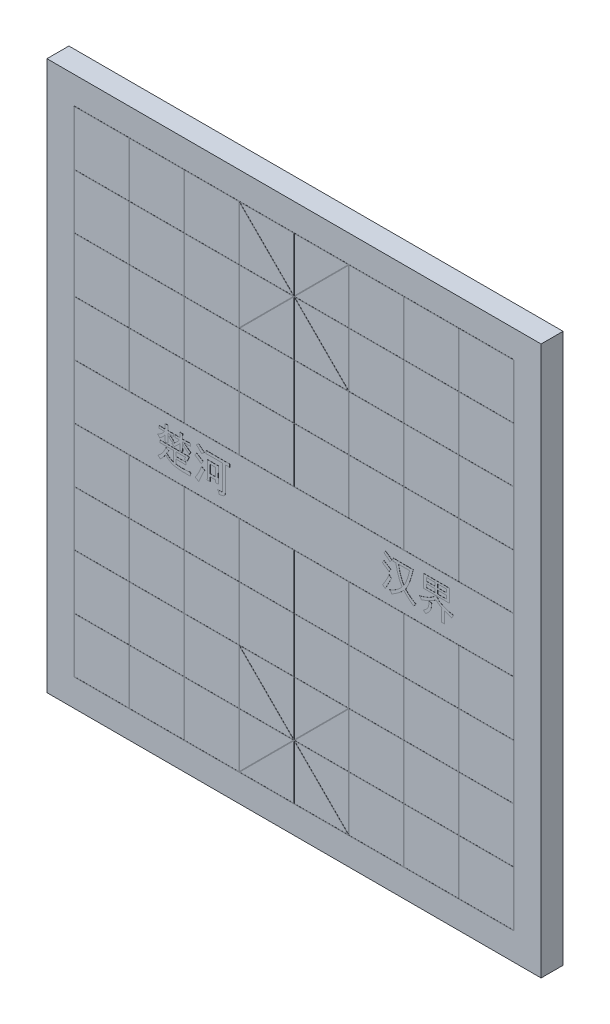
SolidWorks part; units mm, degrees
ref_plane "前视基准面" through (0, 0, 0) normal (0, 0, 1) x (1, 0, 0)
ref_plane "上视基准面" through (0, 0, 0) normal (0, 1, 0) x (1, 0, 0)
ref_plane "右视基准面" through (0, 0, 0) normal (1, 0, 0) x (0, 0, -1)
other "Configuration Table"
sketch "草图1" plane through (0, 0, 0) normal (0, 0, 1) x (1, 0, 0)
  line L1 (-157.5, -175) -> (157.5, -175)
  line L2 (-157.5, -175) -> (-157.5, 175)
  line L3 (-157.5, 175) -> (157.5, 175)
  line L4 (157.5, -175) -> (157.5, 175)
  dimension "D1" = 157.5
  dimension "D2" = 157.5
  dimension "D3" = 175
  dimension "D4" = 175
extrude "Board315x350x14" add sketch "草图1" against normal blind 14
sketch "草图2" plane through (0, 0, 0) normal (0, 0, 1) x (1, 0, 0)
  line L1 (-140, -157.66) -> (140, -157.66)
  line L2 (-140, -157.66) -> (-140, -157.34)
  line L3 (-140, -157.34) -> (140, -157.34)
  line L4 (140, -157.66) -> (140, -157.34)
  line L6 (-140, -122.66) -> (140, -122.66)
  line L7 (-140, -122.66) -> (-140, -122.34)
  line L8 (-140, -122.34) -> (140, -122.34)
  line L9 (140, -122.66) -> (140, -122.34)
  line L11 (-140, -87.66) -> (140, -87.66)
  line L12 (-140, -87.66) -> (-140, -87.34)
  line L13 (-140, -87.34) -> (140, -87.34)
  line L14 (140, -87.66) -> (140, -87.34)
  line L16 (-140, -52.66) -> (140, -52.66)
  line L17 (-140, -52.66) -> (-140, -52.34)
  line L18 (-140, -52.34) -> (140, -52.34)
  line L19 (140, -52.66) -> (140, -52.34)
  line L21 (-140, -17.66) -> (140, -17.66)
  line L22 (-140, -17.66) -> (-140, -17.34)
  line L23 (-140, -17.34) -> (140, -17.34)
  line L24 (140, -17.66) -> (140, -17.34)
  line L26 (-140, 17.34) -> (140, 17.34)
  line L27 (-140, 17.34) -> (-140, 17.66)
  line L28 (-140, 17.66) -> (140, 17.66)
  line L29 (140, 17.34) -> (140, 17.66)
  line L31 (-140, 52.34) -> (140, 52.34)
  line L32 (-140, 52.34) -> (-140, 52.66)
  line L33 (-140, 52.66) -> (140, 52.66)
  line L34 (140, 52.34) -> (140, 52.66)
  line L36 (-140, 87.34) -> (140, 87.34)
  line L37 (-140, 87.34) -> (-140, 87.66)
  line L38 (-140, 87.66) -> (140, 87.66)
  line L39 (140, 87.34) -> (140, 87.66)
  line L41 (-140, 122.34) -> (140, 122.34)
  line L42 (-140, 122.34) -> (-140, 122.66)
  line L43 (-140, 122.66) -> (140, 122.66)
  line L44 (140, 122.34) -> (140, 122.66)
  line L46 (-140, 157.34) -> (140, 157.34)
  line L47 (-140, 157.34) -> (-140, 157.66)
  line L48 (-140, 157.66) -> (140, 157.66)
  line L49 (140, 157.34) -> (140, 157.66)
extrude "Ten_ranks" add sketch "草图2" along normal blind 0.05
sketch "草图3" plane through (0, 0, 0) normal (0, 0, 1) x (1, 0, 0)
  line L1 (-140.16, -157.5) -> (-139.84, -157.5)
  line L2 (-140.16, -157.5) -> (-140.16, 157.5)
  line L3 (-140.16, 157.5) -> (-139.84, 157.5)
  line L4 (-139.84, -157.5) -> (-139.84, 157.5)
  line L6 (-105.16, -157.5) -> (-104.84, -157.5)
  line L7 (-105.16, -157.5) -> (-105.16, -17.5)
  line L8 (-105.16, -17.5) -> (-104.84, -17.5)
  line L9 (-104.84, -157.5) -> (-104.84, -17.5)
  line L11 (-105.16, 17.5) -> (-104.84, 17.5)
  line L12 (-105.16, 17.5) -> (-105.16, 157.5)
  line L13 (-105.16, 157.5) -> (-104.84, 157.5)
  line L14 (-104.84, 17.5) -> (-104.84, 157.5)
  line L16 (-70.16, -157.5) -> (-69.84, -157.5)
  line L17 (-70.16, -157.5) -> (-70.16, -17.5)
  line L18 (-70.16, -17.5) -> (-69.84, -17.5)
  line L19 (-69.84, -157.5) -> (-69.84, -17.5)
  line L21 (-70.16, 17.5) -> (-69.84, 17.5)
  line L22 (-70.16, 17.5) -> (-70.16, 157.5)
  line L23 (-70.16, 157.5) -> (-69.84, 157.5)
  line L24 (-69.84, 17.5) -> (-69.84, 157.5)
  line L26 (-35.16, -157.5) -> (-34.84, -157.5)
  line L27 (-35.16, -157.5) -> (-35.16, -17.5)
  line L28 (-35.16, -17.5) -> (-34.84, -17.5)
  line L29 (-34.84, -157.5) -> (-34.84, -17.5)
  line L31 (-35.16, 17.5) -> (-34.84, 17.5)
  line L32 (-35.16, 17.5) -> (-35.16, 157.5)
  line L33 (-35.16, 157.5) -> (-34.84, 157.5)
  line L34 (-34.84, 17.5) -> (-34.84, 157.5)
  line L36 (-0.16, -157.5) -> (0.16, -157.5)
  line L37 (-0.16, -157.5) -> (-0.16, -17.5)
  line L38 (-0.16, -17.5) -> (0.16, -17.5)
  line L39 (0.16, -157.5) -> (0.16, -17.5)
  line L41 (-0.16, 17.5) -> (0.16, 17.5)
  line L42 (-0.16, 17.5) -> (-0.16, 157.5)
  line L43 (-0.16, 157.5) -> (0.16, 157.5)
  line L44 (0.16, 17.5) -> (0.16, 157.5)
  line L46 (34.84, -157.5) -> (35.16, -157.5)
  line L47 (34.84, -157.5) -> (34.84, -17.5)
  line L48 (34.84, -17.5) -> (35.16, -17.5)
  line L49 (35.16, -157.5) -> (35.16, -17.5)
  line L51 (34.84, 17.5) -> (35.16, 17.5)
  line L52 (34.84, 17.5) -> (34.84, 157.5)
  line L53 (34.84, 157.5) -> (35.16, 157.5)
  line L54 (35.16, 17.5) -> (35.16, 157.5)
  line L56 (69.84, -157.5) -> (70.16, -157.5)
  line L57 (69.84, -157.5) -> (69.84, -17.5)
  line L58 (69.84, -17.5) -> (70.16, -17.5)
  line L59 (70.16, -157.5) -> (70.16, -17.5)
  line L61 (69.84, 17.5) -> (70.16, 17.5)
  line L62 (69.84, 17.5) -> (69.84, 157.5)
  line L63 (69.84, 157.5) -> (70.16, 157.5)
  line L64 (70.16, 17.5) -> (70.16, 157.5)
  line L66 (104.84, -157.5) -> (105.16, -157.5)
  line L67 (104.84, -157.5) -> (104.84, -17.5)
  line L68 (104.84, -17.5) -> (105.16, -17.5)
  line L69 (105.16, -157.5) -> (105.16, -17.5)
  line L71 (104.84, 17.5) -> (105.16, 17.5)
  line L72 (104.84, 17.5) -> (104.84, 157.5)
  line L73 (104.84, 157.5) -> (105.16, 157.5)
  line L74 (105.16, 17.5) -> (105.16, 157.5)
  line L76 (139.84, -157.5) -> (140.16, -157.5)
  line L77 (139.84, -157.5) -> (139.84, 157.5)
  line L78 (139.84, 157.5) -> (140.16, 157.5)
  line L79 (140.16, -157.5) -> (140.16, 157.5)
extrude "Nine_files_with_river" add sketch "草图3" along normal blind 0.06
sketch "草图4" plane through (0, 0, 0) normal (0, 0, 1) x (1, 0, 0)
  line L0 (-34.88, -87.38) -> (35.12, -157.38)
  line L1 (35.12, -157.38) -> (34.88, -157.62)
  line L2 (34.88, -157.62) -> (-35.12, -87.62)
  line L3 (-35.12, -87.62) -> (-34.88, -87.38)
  line L4 (-34.88, 157.62) -> (35.12, 87.62)
  line L5 (35.12, 87.62) -> (34.88, 87.38)
  line L6 (34.88, 87.38) -> (-35.12, 157.38)
  line L7 (-35.12, 157.38) -> (-34.88, 157.62)
extrude "Palace_diagonals_-1" add sketch "草图4" along normal blind 0.07
sketch "草图5" plane through (0, 0, 0) normal (0, 0, 1) x (1, 0, 0)
  line L0 (-34.88, -157.62) -> (35.12, -87.62)
  line L1 (35.12, -87.62) -> (34.88, -87.38)
  line L2 (34.88, -87.38) -> (-35.12, -157.38)
  line L3 (-35.12, -157.38) -> (-34.88, -157.62)
  line L4 (-34.88, 87.38) -> (35.12, 157.38)
  line L5 (35.12, 157.38) -> (34.88, 157.62)
  line L6 (34.88, 157.62) -> (-35.12, 87.62)
  line L7 (-35.12, 87.62) -> (-34.88, 87.38)
extrude "Palace_diagonals_1" add sketch "草图5" along normal blind 0.07
sketch "草图6" plane through (0, 0, 0) normal (0, 0, 1) x (1, 0, 0)
  text T0 "楚河" font "SimHei" height 16
  text T1 "汉界" font "SimHei" height 16
extrude "River_name" add sketch "草图6" along normal blind 0.09
